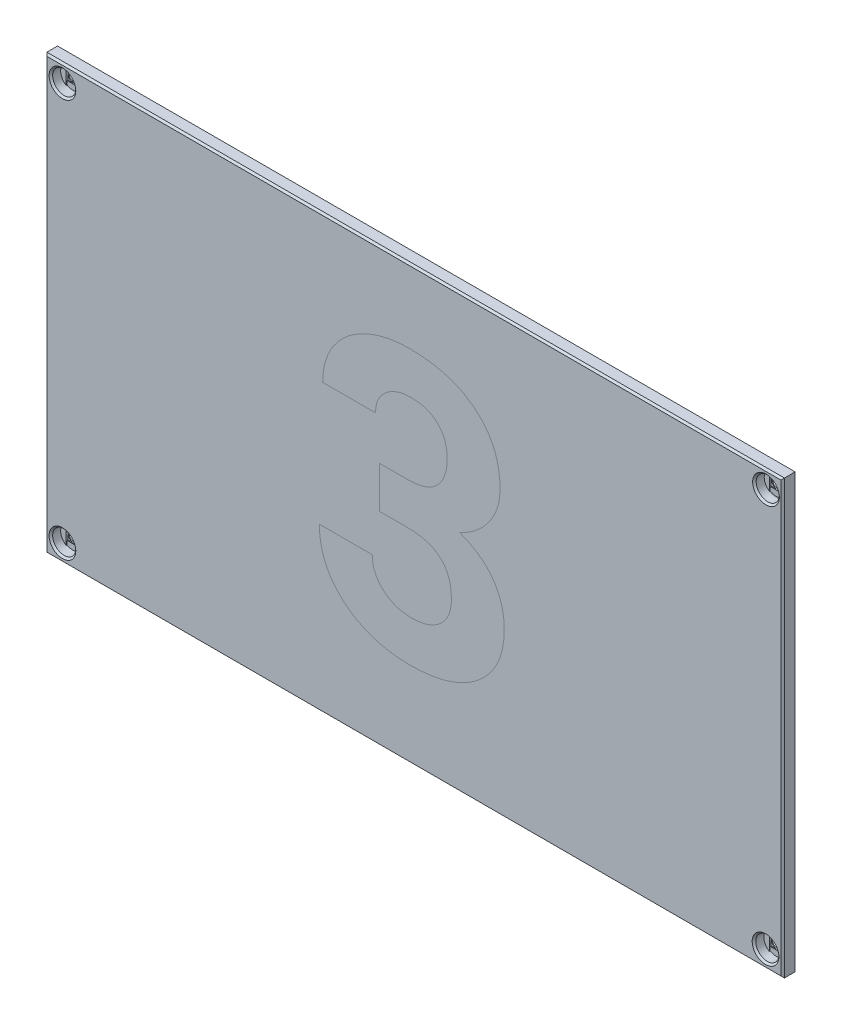
SolidWorks part; units mm, degrees
ref_plane "Front Plane" through (0, 0, 0) normal (0, 0, 1) x (1, 0, 0)
ref_plane "Top Plane" through (0, 0, 0) normal (0, 1, 0) x (1, 0, 0)
ref_plane "Right Plane" through (0, 0, 0) normal (1, 0, 0) x (0, 0, -1)
sketch "Sketch1" plane through (0, 0, 0) normal (0, 0, 1) x (1, 0, 0)
  line L0 (82.95, -11.1) -> (82.95, -18.5) construction
  line L1 (-82.85, -11.1) -> (-82.85, -18.5) construction
  line L2 (-83, -108) -> (-83, -100) construction
  line L3 (-75, -108) -> (-83, -108) construction
  line L4 (75, -108) -> (83, -108) construction
  line L5 (-82.25, -10.5) -> (82.35, -10.5) construction
  line L6 (82.95, -11.1) -> (82.95, -18.5)
  line L7 (-82.85, -11.1) -> (-82.85, -18.5)
  line L8 (-83, -108) -> (-83, -100)
  line L9 (-75, -108) -> (-83, -108)
  line L10 (75, -108) -> (83, -108)
  line L11 (-82.25, -10.5) -> (82.35, -10.5)
  circle A0 centre (-79, -14.5) radius 2.55 construction
  circle A1 centre (79.1, -14.5) radius 2.55
  circle A2 centre (79.1, -14.5) radius 2.55
  circle A3 centre (-79, -104) radius 2.15 construction
  circle A4 centre (79, -104) radius 2.55 construction
  circle A5 centre (-79, -14.5) radius 2.55
  circle A6 centre (-79, -104) radius 2.15
  circle A7 centre (79, -104) radius 2.55
  dimension "D1" = 0
sketch "Sketch2" plane through (0, 0, 0) normal (0, 0, 1) x (1, 0, 0)
  line L0 (-75, -108) -> (-83, -108) construction
  line L1 (-82.9, -10.6) -> (82.85, -10.6)
  line L2 (-82.9, -10.6) -> (-82.9, -107.9)
  line L3 (-82.9, -107.9) -> (82.85, -107.9)
  line L4 (82.85, -10.6) -> (82.85, -107.9)
  line L5 (-83, -108) -> (-83, -100) construction
  line L6 (-82.25, -10.5) -> (82.35, -10.5) construction
  line L7 (82.95, -11.1) -> (82.95, -18.5) construction
  circle A0 centre (-79, -14.5) radius 1.35
  circle A1 centre (79.1, -14.5) radius 1.35
  circle A2 centre (79, -104) radius 1.35
  circle A3 centre (-79, -104) radius 1.35
  point P12 (82.95, -14.8)
  dimension "D5" = 2.7
  dimension "D1" = 0.1
  dimension "D2" = 0.1
  dimension "D3" = 0.1
  dimension "D4" = 0.1
extrude "Boss-Extrude1" add sketch "Sketch2" along normal blind 2.8
sketch "Sketch3" plane through (0, 0, 2.8) normal (0, 0, 1) x (1, 0, 0)
  circle A0 centre (-79, -14.5) radius 2.6
  circle A1 centre (-79, -104) radius 2.6
  circle A2 centre (79, -104) radius 2.6
  circle A3 centre (79.1, -14.5) radius 2.6
  dimension "D1" = 5.2
extrude "Cut-Extrude1" cut sketch "Sketch3" against normal blind 2.2
sketch "Sketch4" plane through (0, 0, 0.6) normal (0, 0, 1) x (1, 0, 0)
  line L6 (-80.35, -16.722) -> (-80.35, -12.278)
  line L8 (-77.65, -16.722) -> (-77.65, -12.278)
  line L9 (-80.35, -16.722) -> (-77.65, -12.278) construction
  line L10 (-80.35, -12.278) -> (-77.65, -16.722) construction
  circle A6 centre (-79, -14.5) radius 2.6 construction
  circle A7 centre (-79, -14.5) radius 1.35 construction
  arc A8 (-77.65, -12.278) -> (-80.35, -12.278) centre (-79, -14.5) ccw
  arc A9 (-80.35, -16.722) -> (-77.65, -16.722) centre (-79, -14.5) ccw
  point P0 (-79, -14.5)
extrude "Cut-Extrude2" cut sketch "Sketch4" against normal blind 0.2
sketch "Sketch5" plane through (0, 0, 0.4) normal (0, 0, 1) x (1, 0, 0)
  line L0 (-77.65, -16.722) -> (-77.65, -12.278) construction
  line L1 (-80.35, -15.85) -> (-77.65, -15.85)
  line L2 (-80.35, -15.85) -> (-80.35, -13.15)
  line L3 (-80.35, -13.15) -> (-77.65, -13.15)
  line L4 (-77.65, -15.85) -> (-77.65, -13.15)
  line L5 (-80.35, -15.85) -> (-77.65, -13.15) construction
  line L6 (-80.35, -13.15) -> (-77.65, -15.85) construction
  arc A0 (-77.65, -14.5) -> (-80.35, -14.5) centre (-79, -14.5) ccw construction
  point P0 (-79, -14.5)
extrude "Cut-Extrude3" cut sketch "Sketch5" against normal blind 0.2
ref_plane "Plane1" through (0, -59.25, 0) normal (0, 1, 0) x (1, 0, 0)
mirror "Mirror1" about plane through (0, -59.25, 0) normal (0, 1, 0) of "Cut-Extrude3", "Cut-Extrude2"
mirror "Mirror2" about plane through (0, 0, 0) normal (1, 0, 0) of "Mirror1"
chamfer "Chamfer1" distance 0.4 angle 45 8 edges at (81.7, -14.5, 2.8) (81.6, -104, 2.8) (-76.4, -104, 2.8) (-76.4, -14.5, 2.8) (-0.025, -107.9, 2.8) (82.85, -59.25, 2.8) (-0.025, -10.6, 2.8) (-82.9, -59.25, 2.8)
sketch "Sketch6" plane through (0, 0, 2.8) normal (0, 0, 1) x (1, 0, 0)
  line L0 (-82.9, -10.6) -> (82.85, -107.9) construction
  line L1 (-23.9, -87.9) -> (19.1939, -87.9) construction
  line L2 (82.85, -107.9) -> (-82.9, -107.9) construction
  line L3 (-82.9, -107.9) -> (-82.9, -10.6) construction
  text T0 "3" font "Roboto" height 60
  point P9 (19.1939, -87.9)
  point P10 (-12.7809, -87.9)
  point P11 (-16.5227, -87.9)
  point P12 (-22.4754, -87.9)
  dimension "D1" = 20
  dimension "D2" = 59
extrude "Cut-Extrude4" cut sketch "Sketch6" against normal blind 1
extrude "Boss-Extrude2" add sketch "Sketch6<2>" against normal up to surface (1 mm away) separate body up to face at (-0.909, -57.3571, 1.8)
sketch "Sketch6<2>" plane through (0, 0, 2.8) normal (0, 0, 1) x (1, 0, 0) same geometry as "Sketch6"
